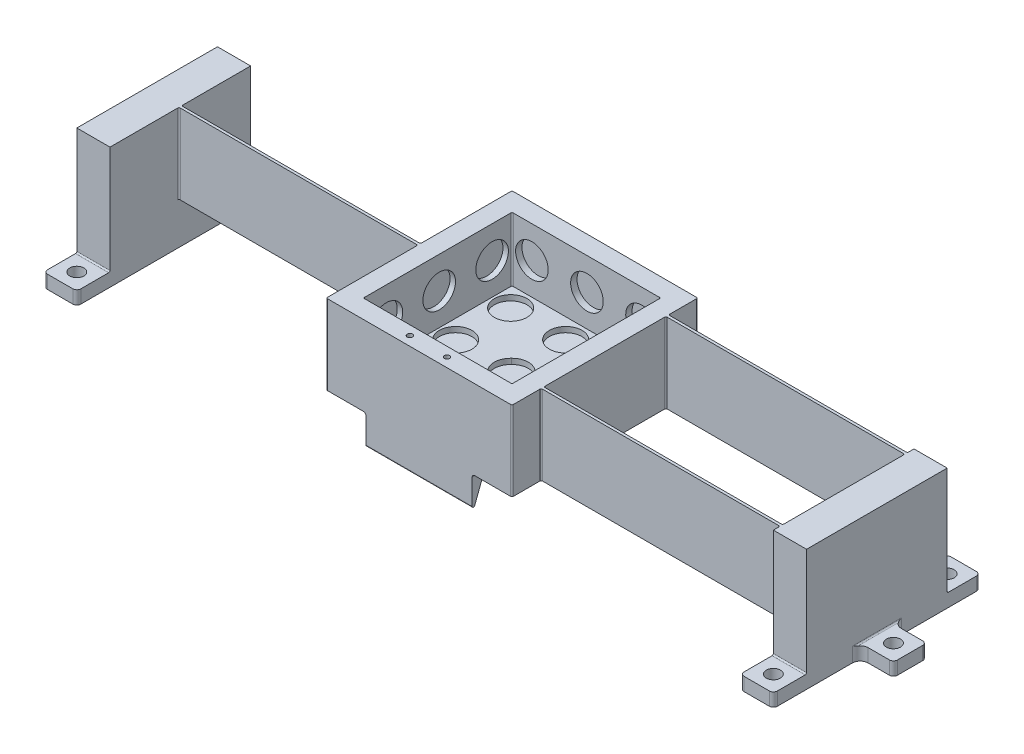
SolidWorks part; units mm, degrees
ref_plane "Front Plane" through (0, 0, 0) normal (0, 0, 1) x (1, 0, 0)
ref_plane "Top Plane" through (0, 0, 0) normal (0, 1, 0) x (1, 0, 0)
ref_plane "Right Plane" through (0, 0, 0) normal (1, 0, 0) x (0, 0, -1)
sketch "Sketch1" plane through (0, 0, 0) normal (0, 1, 0) x (1, 0, 0)
  line L1 (-35, -35) -> (35, -35)
  line L2 (-35, -35) -> (-35, 35)
  line L3 (-35, 35) -> (35, 35)
  line L4 (35, -35) -> (35, 35)
  line L5 (-35, -35) -> (35, 35) construction
  line L6 (-35, 35) -> (35, -35) construction
  point P0 (0, 0)
  dimension "D1" = 70
  dimension "D2" = 70
extrude "Boss-Extrude1" add sketch "Sketch1" along normal blind 30
shell "Shell1" thickness 7 removed face at (0, 30, 0)
sketch "Sketch2" plane through (0, 30, 0) normal (0, 1, 0) x (1, 0, 0)
  line L0 (-35, 35) -> (-35, -35) construction
  line L1 (-28, -28) -> (28, -28) construction
  line L2 (-28, -28) -> (-28, 28) construction
  line L3 (-28, 28) -> (28, 28) construction
  line L4 (28, -28) -> (28, 28) construction
  line L5 (-28, -28) -> (28, 28) construction
  line L6 (-28, 28) -> (28, -28) construction
  line L7 (35, 35) -> (-35, 35) construction
  point P0 (0, 0)
  dimension "D1" = 7
  dimension "D2" = 7
sketch "Sketch3" plane through (35, 0, 0) normal (1, 0, 0) x (0, 0, -1)
  line L0 (-35, 30) -> (35, 30) construction
  line L1 (-24, 30) -> (-23, 30)
  line L2 (-24, 30) -> (-24, 0)
  line L3 (-24, 0) -> (-23, 0)
  line L4 (-23, 30) -> (-23, 0)
  line L5 (-35, 0) -> (35, 0) construction
  line L6 (-28, 30) -> (28, 30) construction
  line L7 (-0.5, 30) -> (0.5, 30)
  line L8 (-0.5, 30) -> (-0.5, 0)
  line L9 (-0.5, 0) -> (0.5, 0)
  line L10 (0.5, 30) -> (0.5, 0)
  line L11 (28, 30) -> (-28, 30) construction
  line L12 (24, 30) -> (23, 30)
  line L13 (24, 30) -> (24, 0)
  line L14 (24, 0) -> (23, 0)
  line L15 (23, 30) -> (23, 0)
  line L16 (-23.5, 30) -> (-23.5, 0) construction
  line L17 (0, 30) -> (0, 0) construction
  line L18 (23.5, 0) -> (23.5, 30) construction
  dimension "D1" = 23
  dimension "D2" = 23
  dimension "D3" = 1
extrude "Boss-Extrude2" add sketch "Sketch3" along normal blind 90
sketch "Sketch5" plane through (125, 0, 0) normal (1, 0, 0) x (0, 0, -1)
  line L0 (-24, 30) -> (-24, 0) construction
  line L1 (-26.5, 30) -> (26.5, 30)
  line L2 (-26.5, 30) -> (-26.5, 0)
  line L3 (-26.5, 0) -> (26.5, 0)
  line L4 (26.5, 30) -> (26.5, 0)
  line L5 (28, 30) -> (-28, 30) construction
  line L6 (24, 0) -> (35, 0) construction
  line L7 (24, 0) -> (24, 30) construction
  dimension "D1" = 2.5
  dimension "D2" = 2.5
extrude "Boss-Extrude3" add sketch "Sketch5" along normal blind 12.5
sketch "Sketch6" plane through (0, 0, 0) normal (0, -1, 0) x (1, 0, 0)
  line L1 (125, 26.5) -> (137.5, 26.5)
  line L2 (125, 26.5) -> (125, -26.5)
  line L3 (125, -26.5) -> (137.5, -26.5)
  line L4 (137.5, 26.5) -> (137.5, -26.5)
extrude "Boss-Extrude4" add sketch "Sketch6" along normal blind 15.75
sketch "Sketch8" plane through (0, -15.75, 0) normal (0, -1, 0) x (1, 0, 0)
  line L1 (137.5, -26.5) -> (125, -26.5)
  line L2 (137.5, -26.5) -> (137.5, -39)
  line L3 (137.5, -39) -> (125, -39)
  line L4 (125, -26.5) -> (125, -39)
  line L5 (137.5, 26.5) -> (125, 26.5)
  line L6 (137.5, 26.5) -> (137.5, 39)
  line L7 (137.5, 39) -> (125, 39)
  line L8 (125, 26.5) -> (125, 39)
  line L13 (137.5, -26.5) -> (137.5, 26.5) construction
  line L14 (150, -6.25) -> (137.5, -6.25)
  line L15 (150, -6.25) -> (150, 6.25)
  line L16 (150, 6.25) -> (137.5, 6.25)
  line L17 (137.5, -6.25) -> (137.5, 6.25)
  line L18 (150, -6.25) -> (137.5, 6.25) construction
  line L19 (150, 6.25) -> (137.5, -6.25) construction
  line L20 (125, 0) -> (150, 0) construction
  line L21 (125, 0.5) -> (125, -0.5) construction
  point P13 (143.75, 0)
  point P19 (137.5, 0)
  point P20 (137.5, 0)
extrude "Boss-Extrude5" add sketch "Sketch8" against normal blind 5
hole_wizard "Ø5.0mm Dowel Hole1" positions "Sketch9" profile "Sketch10" hole size "Ø5.0" standard "ANSI Metric"
sketch "Sketch9" plane through (0, -10.75, 0) normal (0, 1, 0) x (1, 0, 0)
  line L0 (131.25, 39) -> (131.25, 32.75) construction
  line L1 (125, 39) -> (137.5, 39) construction
  line L2 (131.25, 32.75) -> (137.5, 32.75) construction
  line L3 (137.5, 39) -> (137.5, 26.5) construction
  line L5 (137.5, 0) -> (143.75, 0) construction
  line L6 (137.5, -6.25) -> (137.5, 6.25) construction
  line L7 (143.75, 0) -> (143.75, 6.25) construction
  line L8 (137.5, 6.25) -> (150, 6.25) construction
  line L10 (131.25, -26.5) -> (131.25, -32.75) construction
  line L11 (125, -26.5) -> (137.5, -26.5) construction
  line L12 (131.25, -32.75) -> (137.5, -32.75) construction
  line L13 (137.5, -26.5) -> (137.5, -39) construction
  point P0 (131.25, 32.75)
  point P2 (143.75, 0)
  point P4 (131.25, -32.75)
sketch "Sketch10" plane through (131.25, -10.75, -32.75) normal (1, 0, 0) x (0, 0, 1)
  line L0 (0, 0) -> (0, 18.1023)
  line L1 (0, 18.1023) -> (2.65, 16.51)
  line L2 (2.65, 16.51) -> (2.65, 0)
  line L5 (2.65, 0) -> (0, 0)
  line L10 (0, 18.1023) -> (-2.65, 16.51) construction
  line L11 (0, -6.35) -> (0, 107.95) construction
  dimension "Hole Dia." = 5.3
  dimension "Hole Depth" = 16.51
  dimension "Drill Angle" = 118
mirror "Mirror1" about plane through (0, 0, 0) normal (1, 0, 0) of "Boss-Extrude2", "Boss-Extrude3", "Boss-Extrude5", "Boss-Extrude4", "Ø5.0mm Dowel Hole1"
sketch "Sketch25" plane through (0, 30, 0) normal (0, 1, 0) x (1, 0, 0)
  line L1 (-125, 24) -> (-35, 24)
  line L2 (-125, 24) -> (-125, 23)
  line L3 (-125, 23) -> (-35, 23)
  line L4 (-35, 24) -> (-35, 23)
  line L5 (-125, -23) -> (-35, -23)
  line L6 (-125, -23) -> (-125, -24)
  line L7 (-125, -24) -> (-35, -24)
  line L8 (-35, -23) -> (-35, -24)
extrude "Cut-Extrude7" cut sketch "Sketch25" against normal through all both and the other way through all
fillet "Fillet2" radius 1.5 12 edges at (150, -13.25, 6.25) (150, -13.25, -6.25) (137.5, -13.25, -39) (125, -13.25, -39) (137.5, -13.25, 39) (125, -13.25, 39) (-125, -13.25, -39) (-137.5, -13.25, -39) (-150, -13.25, -6.25) (-150, -13.25, 6.25) (-125, -13.25, 39) (-137.5, -13.25, 39)
sketch "Sketch11" plane through (0, 6, 0) normal (0, 1, 0) x (1, 0, 0)
  line L26 (-28, -28) -> (-28, 28) construction
  line L32 (-28, -28) -> (28, -28) construction
  circle A0 centre (-21, -21) radius 6.15
  dimension "D1" = 12.3
  dimension "D2" = 0.85
  dimension "D3" = 0.85
extrude "Cut-Extrude1" cut sketch "Sketch11" against normal blind 2.05
pattern_linear "LPattern1" count 3 spacing 20.75 along (1, 0, 0) count 3 spacing 20.75 along (0, 0, -1) of "Cut-Extrude1"
sketch "Sketch14" plane through (0, 6, 0) normal (0, 1, 0) x (1, 0, 0)
  line L0 (-28, 0) -> (0, 0) construction
  line L1 (-28, 28) -> (-28, -28) construction
  line L2 (0, 0) -> (0, -28) construction
  line L3 (-28, -28) -> (28, -28) construction
  circle A0 centre (0, 0) radius 6.15
  dimension "D1" = 12.3
extrude "Cut-Extrude4" cut sketch "Sketch14" against normal blind 2.05
sketch "Sketch12" plane through (-28, 0, 0) normal (1, 0, 0) x (0, 0, -1)
  line L5 (-28, 18) -> (-19.35, 18) construction
  line L6 (-28, 30) -> (-28, 6) construction
  circle A0 centre (-19.35, 18) radius 6.15
  dimension "D1" = 12.3
  dimension "D2" = 2.5
extrude "Cut-Extrude2" cut sketch "Sketch12" against normal blind 2.05
pattern_linear "LPattern2" count 3 spacing 19.925 along (0, 0, -1) of "Cut-Extrude2"
sketch "Sketch13" plane through (0, 0, -28) normal (0, 0, -1) x (-1, 0, 0)
  line L6 (-28, 30) -> (-28, 6) construction
  line L7 (-21, 18) -> (-28, 18) construction
  circle A0 centre (-21, 18) radius 6.15
  dimension "D1" = 12.3
  dimension "D3" = 0.85
extrude "Cut-Extrude3" cut sketch "Sketch13" along normal blind 2.4
pattern_linear "LPattern3" count 3 spacing 20.75 along (-1, 0, 0) of "Cut-Extrude3"
mirror "Mirror2" about plane through (0, 0, 0) normal (1, 0, 0) of "LPattern2", "Cut-Extrude2"
sketch "Sketch24" plane through (0, 30, 0) normal (0, 1, 0) x (1, 0, 0)
  line L1 (35, 0.5) -> (125, 0.5)
  line L2 (35, 0.5) -> (35, -0.5)
  line L3 (35, -0.5) -> (125, -0.5)
  line L4 (125, 0.5) -> (125, -0.5)
extrude "Cut-Extrude6" cut sketch "Sketch24" against normal through all both and the other way through all
fillet "Fillet4" radius 0.5 4 edges at (-35, 15, 35) (35, 15, 35) (-35, 15, -35) (35, 15, -35)
sketch "Sketch19" plane through (0, 0, 0) normal (1, 0, 0) x (0, 0, -1)
  line L0 (-30, 0) -> (-35, -13.25)
  line L1 (-35, -13.25) -> (-35, 0)
  line L2 (-35, 0) -> (-30, 0)
  line L3 (0, 0) -> (-30, 0) construction
  line L4 (37.5, -15.75) -> (-37.5, -15.75) construction
  dimension "D1" = 5
  dimension "D2" = 30
  dimension "D3" = 2.5
extrude "Boss-Extrude8" add sketch "Sketch19" along normal mid plane 40
sketch "Sketch20" plane through (0, 0, 0) normal (1, 0, 0) x (0, 0, -1)
  line L0 (-35, 20) -> (-42.5, 20)
  line L1 (-42.5, 20) -> (-42.5, 30)
  line L2 (-26.5, 30) -> (-42.5, 30) construction
  line L5 (-42.5, 30) -> (-40, 30)
  line L6 (-40, 30) -> (-40, 22.5)
  line L7 (-40, 22.5) -> (-35, 22.5)
  line L8 (-35, 22.5) -> (-35, 20)
  line L9 (-35, 30) -> (-35, 0) construction
  line L10 (-35, 0) -> (-35, 30) construction
  dimension "D1" = 5
  dimension "D2" = 10
  dimension "D3" = 2.5
  dimension "D4" = 2.5
extrude "Place For Sensor" [suppressed] add sketch "Sketch20" along normal mid plane 10
fillet "Place For Sensor Fillet5" [suppressed] radius 0.5
fillet "Place For Sensor Fillet6" [suppressed] radius 1.5
hole_wizard "Place For Sensor Ø3.0mm Dowel Hole2" [suppressed] positions "Sketch21" profile "Sketch22" hole size "Ø3.0" standard "ANSI Metric"
sketch "Sketch21" [suppressed] plane through (0, 0, 32.5) normal (0, 0, 1) x (1, 0, 0)
  line L0 (-2.5, 27.5) -> (2.5, 27.5) construction
  line L2 (-18, 30) -> (18, 30) construction
  line L3 (-5, 28.5) -> (-5, 20.5) construction
  line L4 (5, 28.5) -> (5, 20.5) construction
  point P0 (-2.5, 27.5)
  point P2 (2.5, 27.5)
  dimension "D1" = 2.5
  dimension "D2" = 2.5
  dimension "D3" = 2.5
sketch "Sketch22" plane through (-2.5, 27.5, 32.5) normal (1, 0, 0) x (0, -1, 0)
  line L0 (0, 0) -> (0, 2.5)
  line L1 (0, 2.5) -> (1.65, 2.5)
  line L2 (1.65, 2.5) -> (1.65, 0)
  line L5 (1.65, 0) -> (0, 0)
  line L11 (0, -6.35) -> (0, 107.95) construction
  dimension "Thru Hole Dia." = 3.3
  dimension "Thru Hole Depth" = 2.5
sketch "Sketch23" plane through (0, 30, 0) normal (0, 1, 0) x (1, 0, 0)
  line L1 (-28, -28) -> (28, -28) construction
  circle A0 centre (-7, -31.5) radius 1
  circle A1 centre (7, -31.5) radius 1
  dimension "D4" = 2
  dimension "D1" = 3.5
  dimension "D2" = 14
  dimension "D3" = 7
extrude "Cut-Extrude5" cut sketch "Sketch23" against normal blind 6
fillet "Fillet3" radius 0.5 4 edges at (28, 18, -28) (-28, 18, -28) (28, 18, 28) (-28, 18, 28)
fillet "Fillet1" radius 0.5 16 edges at (131.25, -10.75, -26.5) (131.25, -10.75, 26.5) (-125, 15, 0.5) (-125, 15, -0.5) (-35, 15, 0.5) (-35, 15, -0.5) (-131.25, -10.75, -26.5) (-131.25, -10.75, 26.5) (35, 15, 24) (35, 15, 23) (125, 15, 24) (125, 15, 23) (35, 15, -24) (35, 15, -23) (125, 15, -24) (125, 15, -23)
fillet "Fillet5" radius 0.5 1 edges at (0, -13.25, 35)
fillet "Fillet6" radius 1 3 edges at (-20, 0, 32.5) (20, 0, 32.5) (0, 0, 30)
fillet "Fillet8" radius 3 4 edges at (137.5, -13, 6.25) (137.5, -13, -6.25) (-137.5, -13, -6.25) (-137.5, -13, 6.25)
